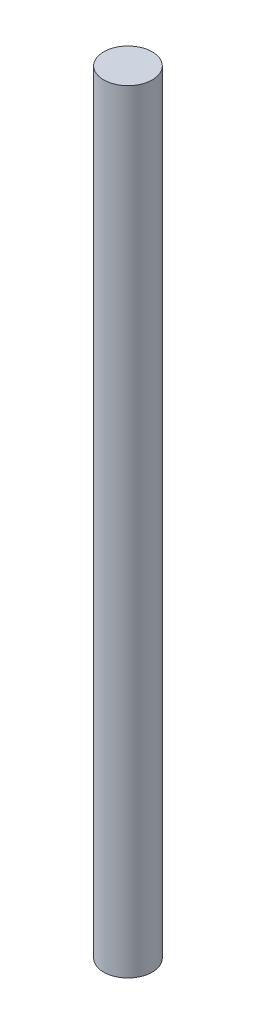
SolidWorks part; units mm, degrees
ref_plane "前视基准面" through (0, 0, 0) normal (0, 0, 1) x (1, 0, 0)
ref_plane "上视基准面" through (0, 0, 0) normal (0, 1, 0) x (1, 0, 0)
ref_plane "右视基准面" through (0, 0, 0) normal (1, 0, 0) x (0, 0, -1)
other "Configuration Table"
sketch "草图1" plane through (0, 0, 0) normal (0, 1, 0) x (1, 0, 0)
  circle A0 centre (0, 0) radius 1
  dimension "D1" = 2
extrude "凸台-拉伸1" add sketch "草图1" along normal mid plane 31.8
